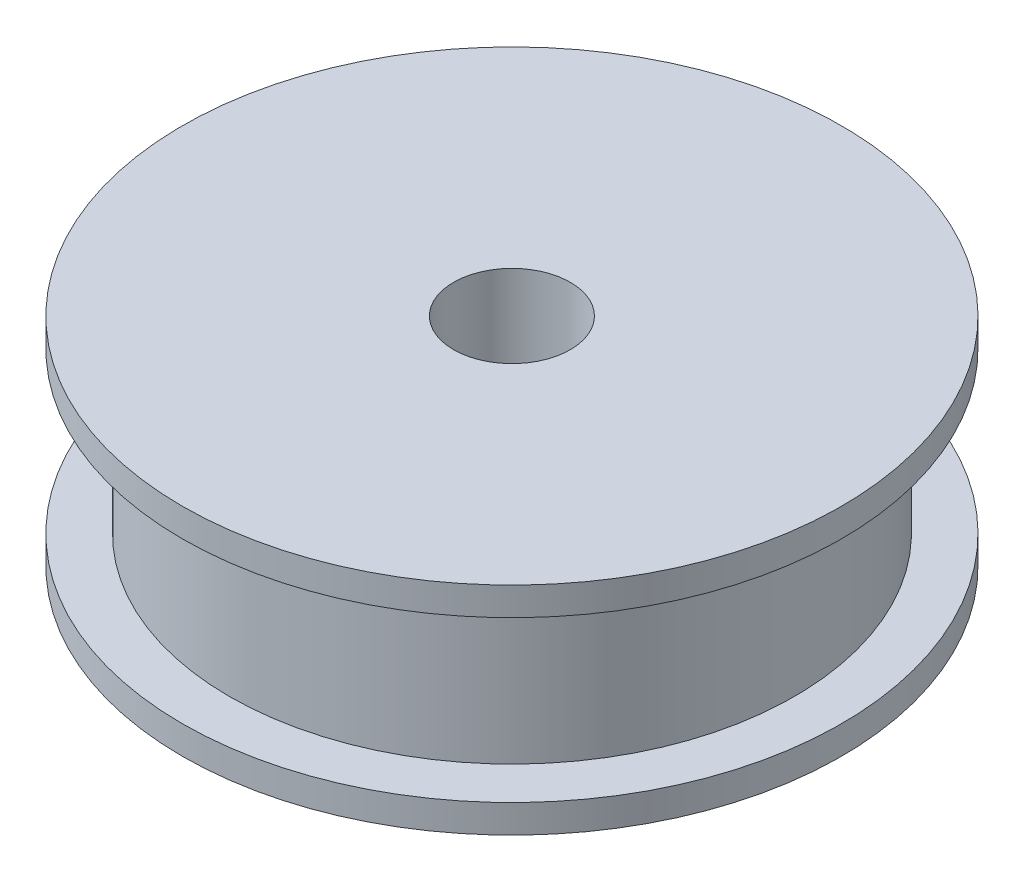
SolidWorks part; units mm, degrees
ref_plane "前视基准面" through (0, 0, 0) normal (0, 0, 1) x (1, 0, 0)
ref_plane "上视基准面" through (0, 0, 0) normal (0, 1, 0) x (1, 0, 0)
ref_plane "右视基准面" through (0, 0, 0) normal (1, 0, 0) x (0, 0, -1)
sketch "内环" plane through (0, 0, 0) normal (0, 1, 0) x (1, 0, 0)
  circle A0 centre (0, 0) radius 15
extrude "凸台-拉伸1" add sketch "内环" along normal mid plane 10
sketch "边缘" plane through (0, 0, 0) normal (0, 1, 0) x (1, 0, 0)
  circle A0 centre (0, 0) radius 17.5
extrude "边缘1" add sketch "边缘" along normal blind 1.5 from surface starting at face at (0, 5, 15)
extrude "边缘2" add sketch "草图2<2>" along normal blind 1.5 from surface starting at face at (0, -5, 15)
sketch "草图2<2>" plane through (0, 0, 0) normal (0, 1, 0) x (1, 0, 0) same geometry as "边缘"
sketch "孔" plane through (0, 0, 0) normal (0, 1, 0) x (1, 0, 0)
  circle A0 centre (0, 0) radius 3.1
  dimension "D1" = 6.2
extrude "切除-拉伸1" cut sketch "孔" against normal mid plane 13
